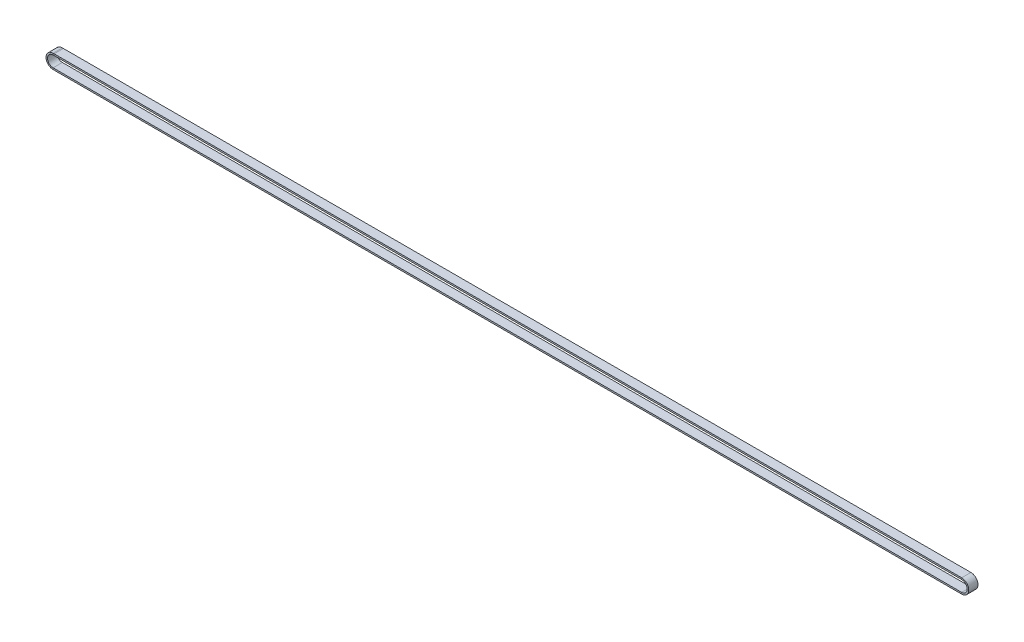
SolidWorks part; units mm, degrees
ref_plane "Front Plane" through (0, 0, 0) normal (0, 0, 1) x (1, 0, 0)
ref_plane "Top Plane" through (0, 0, 0) normal (0, 1, 0) x (1, 0, 0)
ref_plane "Right Plane" through (0, 0, 0) normal (1, 0, 0) x (0, 0, -1)
sketch "Sketch2" plane through (0, 0, -46.13) normal (0, 0, 1) x (1, 0, 0)
  line L0 (0, 0) -> (1, 0) construction
  line L1 (0, 0) -> (0, 1) construction
  line L2 (-1, 18.4186) -> (883.5206, 18.4186)
  line L3 (883.5206, 4.6186) -> (-1, 4.6186)
  arc A0 (-1, 4.6186) -> (-1, 18.4186) centre (-1, 11.5186) cw
  arc A1 (883.5206, 18.4186) -> (883.5206, 4.6186) centre (883.5206, 11.5186) cw
sketch "Sketch3" plane through (0, 0, 0) normal (1, 0, 0) x (0, 0, -1)
  line L1 (46.13, 16.9186) -> (37.13, 16.9186)
  line L2 (46.13, 16.9186) -> (46.13, 18.4186)
  line L3 (46.13, 18.4186) -> (37.13, 18.4186)
  line L4 (37.13, 16.9186) -> (37.13, 18.4186)
  dimension "D1" = 9
  dimension "D2" = 1.5
sweep "Sweep1" add profiles "Sketch3" path "Sketch2"
